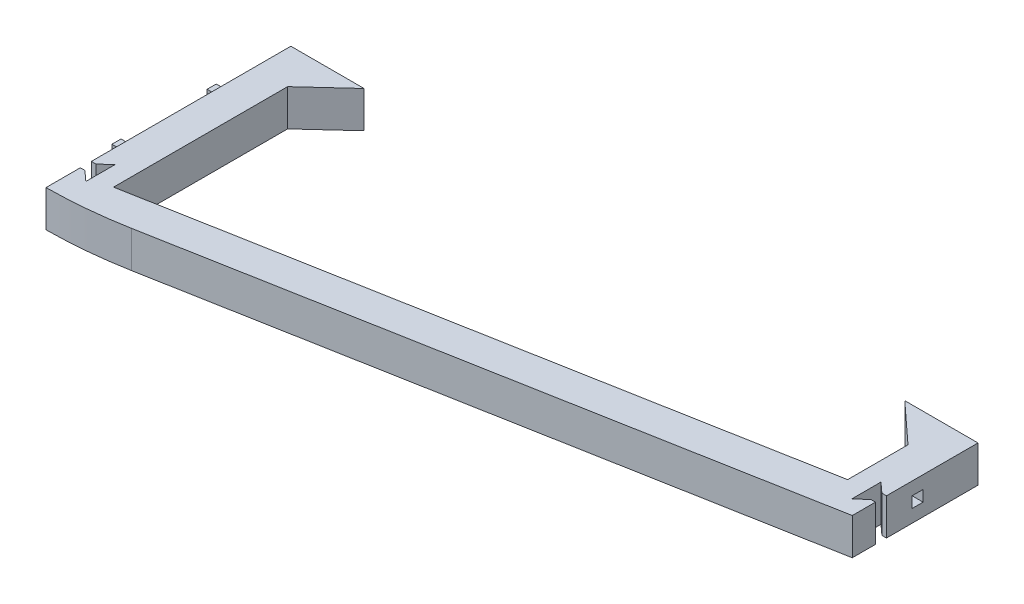
SolidWorks part; units mm, degrees
ref_plane "Přední rovina" through (0, 0, 0) normal (0, 0, 1) x (1, 0, 0)
ref_plane "Horní rovina" through (0, 0, 0) normal (0, 1, 0) x (1, 0, 0)
ref_plane "Pravá rovina" through (0, 0, 0) normal (1, 0, 0) x (0, 0, -1)
sketch "Skica1" plane through (0, 0, 0) normal (0, 1, 0) x (1, 0, 0)
  line L0 (0, 0) -> (0, -55)
  line L1 (0, -55) -> (150.15, -27.4721)
  line L2 (150.15, -27.4721) -> (150.15, 0)
  line L3 (150.15, 0) -> (142.85, 0)
  line L4 (142.85, 0) -> (142.85, -21.1855)
  line L5 (142.85, -21.1855) -> (7.3, -46.0366)
  line L6 (7.3, -46.0366) -> (7.3, 0)
  line L7 (7.3, 0) -> (0, 0)
  dimension "D1" = 7.3
  dimension "D2" = 7.3
  dimension "D3" = 55
  dimension "D4" = 7.5
  dimension "D5" = 150.15
  dimension "D6" = 27.4721
extrude "Přidat vysunutím1" add sketch "Skica1" along normal blind 8
sketch "Skica2" plane through (0, 8, 0) normal (0, 1, 0) x (1, 0, 0)
  line L5 (0, -43.6) -> (1, -43.6)
  line L6 (0, 0) -> (0, -55) construction
  line L7 (1, -43.6) -> (3.2, -41.6)
  line L8 (3.2, -41.6) -> (3.2, -48)
  line L9 (3.2, -48) -> (1, -46)
  line L10 (1, -46) -> (0, -46)
  line L11 (0, -46) -> (0, -43.6)
  dimension "D1" = 6.4
  dimension "D2" = 2.4
  dimension "D3" = 1
  dimension "D4" = 1
  dimension "D5" = 2
  dimension "D6" = 3.2
  dimension "D7" = 7
extrude "Odebrat vysunutím1" cut sketch "Skica2" against normal through all
sketch "Skica3" plane through (0, 0, 0) normal (-1, 0, 0) x (0, 0, 1)
  line L0 (0, 8) -> (0, 0) construction
  line L1 (12.3, 5) -> (14.3, 5)
  line L2 (12.3, 5) -> (12.3, 3)
  line L3 (12.3, 3) -> (14.3, 3)
  line L4 (14.3, 5) -> (14.3, 3)
  line L5 (33.1, 5) -> (35.1, 5)
  line L6 (33.1, 5) -> (33.1, 3)
  line L7 (33.1, 3) -> (35.1, 3)
  line L8 (35.1, 5) -> (35.1, 3)
  line L17 (0, 8) -> (43.6, 8) construction
  point P16 (12.3, 4)
  dimension "D1" = 12.3
  dimension "D2" = 2
  dimension "D3" = 2
  dimension "D4" = 3
  dimension "D5" = 2
  dimension "D6" = 2
  dimension "D7" = 3
  dimension "D8" = 18.8
extrude "Přidat vysunutím2" add sketch "Skica3" along normal blind 4
sketch "Skica5" plane through (0, 8, 0) normal (0, 1, 0) x (1, 0, 0)
  line L0 (0, 0) -> (0, -43.6) construction
  line L1 (0, 0) -> (16, 0)
  line L2 (0, 0) -> (0, -8)
  line L3 (0, -8) -> (16, -8)
  line L4 (16, 0) -> (16, -8)
  line L5 (150.15, -27.4721) -> (150.15, 0) construction
  line L6 (150.15, 0) -> (134.15, 0)
  line L7 (150.15, 0) -> (150.15, -8)
  line L8 (150.15, -8) -> (134.15, -8)
  line L9 (134.15, 0) -> (134.15, -8)
  line L12 (7.3, 0) -> (0, 0) construction
  line L13 (150.15, 0) -> (142.85, 0) construction
  dimension "D1" = 8
  dimension "D2" = 8
  dimension "D3" = 16
  dimension "D4" = 16
extrude "Přidat vysunutím3" add sketch "Skica5" against normal blind 8
sketch "Skica7" plane through (0, 0, 0) normal (0, -1, 0) x (1, 0, 0)
  line L0 (7.3, 8) -> (16, 0)
  line L1 (16, 0) -> (16, 8)
  line L2 (16, 8) -> (7.3, 8)
  line L3 (134.15, 0) -> (134.15, 8)
  line L4 (134.15, 8) -> (142.85, 8)
  line L5 (142.85, 8) -> (134.15, 0)
extrude "Odebrat vysunutím4" cut sketch "Skica7" against normal through all
sketch "Skica4" plane through (150.15, 0, 0) normal (1, 0, 0) x (0, 0, -1)
  line L0 (-27.4721, 8) -> (0, 8) construction
  line L5 (-14.4, 5.2) -> (-12, 5.2)
  line L6 (-14.4, 5.2) -> (-14.4, 2.8)
  line L7 (-14.4, 2.8) -> (-12, 2.8)
  line L8 (-12, 5.2) -> (-12, 2.8)
  line L13 (0, 8) -> (0, 0) construction
  dimension "D1" = 2.4
  dimension "D2" = 2.4
  dimension "D3" = 2.8
  dimension "D4" = 12
extrude "Odebrat vysunutím2" cut sketch "Skica4" against normal blind 4.4
sketch "Skica8" plane through (0, 8, 0) normal (0, 1, 0) x (1, 0, 0)
  line L6 (150.15, -20) -> (149.15, -20)
  line L7 (150.15, -27.4721) -> (150.15, 0) construction
  line L8 (149.15, -20) -> (146.95, -18)
  line L9 (146.95, -18) -> (146.95, -24.4)
  line L10 (146.95, -24.4) -> (149.15, -22.4)
  line L11 (150.15, -22.4) -> (150.15, -20)
  line L12 (149.15, -22.4) -> (150.15, -22.4)
  line L13 (150.15, 0) -> (134.15, 0) construction
  point P10 (142.15, 0)
  dimension "D1" = 6.4
  dimension "D2" = 1
  dimension "D3" = 2.4
  dimension "D4" = 2
  dimension "D5" = 3.2
  dimension "D6" = 18
  dimension "D7" = 1
extrude "Odebrat vysunutím5" cut sketch "Skica8" against normal through all
sketch "Skica9" plane through (0, 8, 0) normal (0, 1, 0) x (1, 0, 0)
  line L0 (0, -53.5) -> (8.1817, -53.5)
  line L1 (0, -46) -> (0, -55) construction
  line L2 (0, -55) -> (150.15, -27.4721) construction
  line L3 (8.1817, -53.5) -> (0, -55)
  line L4 (0, -55) -> (0, -53.5)
  dimension "D1" = 1.5
extrude "Odebrat vysunutím6" cut sketch "Skica9" against normal through all
fillet "Zaoblit1" radius 100 1 edges at (8.1817, 4, 53.5)
sketch "Skica11" plane through (0, 0, 0) normal (0, 0, -1) x (-1, 0, 0)
  line L0 (-150.15, 0) -> (-134.15, 0) construction
  line L2 (-150.15, 8) -> (-150.15, 0) construction
  line L3 (-16, 8) -> (0, 8) construction
  line L4 (0, 8) -> (0, 0) construction
  circle A0 centre (-146.5, 4) radius 2.2
  circle A1 centre (-3.65, 4) radius 2.2
  dimension "D1" = 4.4
  dimension "D4" = 4.4
  dimension "D2" = 4
  dimension "D3" = 3.65
  dimension "D5" = 4
  dimension "D6" = 3.65
extrude "Odebrat vysunutím7" cut sketch "Skica11" against normal blind 2.4
sketch "Skica12" plane through (0, 0, 2.4) normal (0, 0, -1) x (-1, 0, 0)
  circle A0 centre (-146.5, 4) radius 1.85
  circle A1 centre (-3.65, 4) radius 1.85
  dimension "D1" = 3.7
  dimension "D2" = 3.7
extrude "Odebrat vysunutím8" cut sketch "Skica12" against normal blind 7
